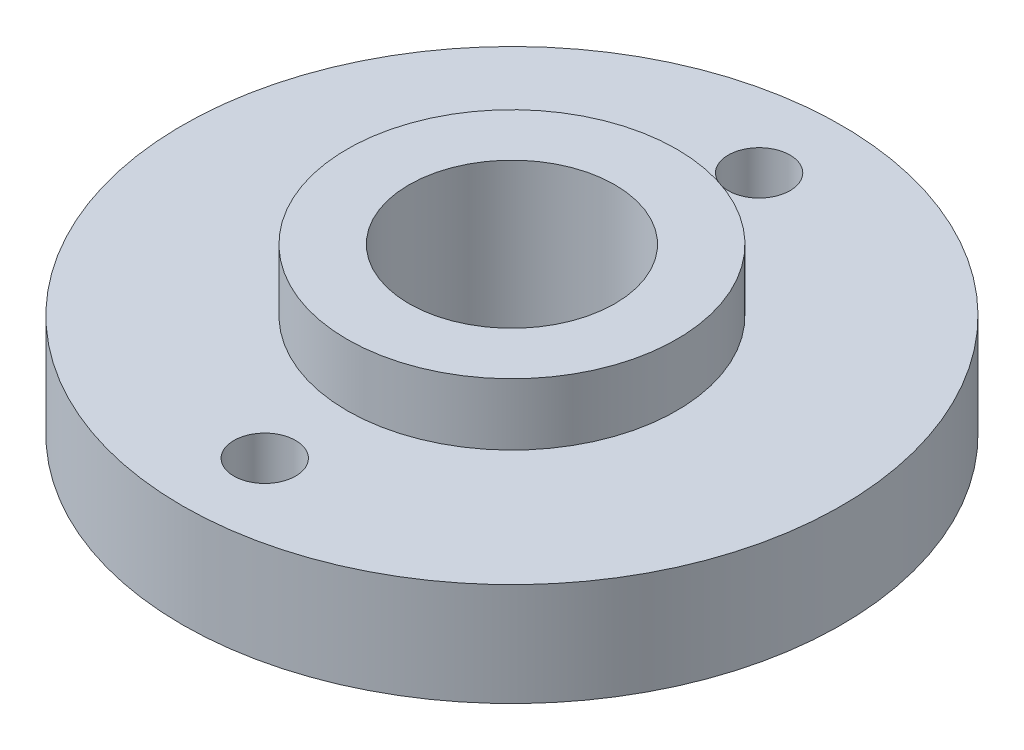
SolidWorks part; units mm, degrees
ref_plane "Спереди" through (0, 0, 0) normal (0, 0, 1) x (1, 0, 0)
ref_plane "Сверху" through (0, 0, 0) normal (0, 1, 0) x (1, 0, 0)
ref_plane "Справа" through (0, 0, 0) normal (1, 0, 0) x (0, 0, -1)
sketch "Эскиз2" plane through (0, 0, 0) normal (1, 0, 0) x (0, 0, -1)
  line L0 (0, 18.0956) -> (0, 0) construction
  line L1 (5, 0) -> (16, 0)
  line L2 (16, 0) -> (16, 5)
  line L3 (16, 5) -> (8, 5)
  line L4 (8, 5) -> (8, 8)
  line L5 (8, 8) -> (5, 8)
  line L6 (5, 8) -> (5, 0)
  dimension "D1" = 5
  dimension "D2" = 8
  dimension "D3" = 3
  dimension "D4" = 5
  dimension "D5" = 3
revolve "Повернуть1" add sketch "Эскиз2" angle 360 about L0
sketch "Эскиз3" plane through (0, 5, 0) normal (0, 1, 0) x (1, 0, 0)
  line L0 (0, 22.2403) -> (0, -28.6554) construction
  line L1 (-26.0144, 0) -> (30.2926, 0) construction
  circle A0 centre (0, 12) radius 1.5
  circle A1 centre (0, -12) radius 1.5
  circle A6 centre (0, 0) radius 12
  point P7 (0, 0)
  point P10 (0, 0)
  dimension "D1" = 3
  dimension "D2" = 3
  dimension "D3" = 12
extrude "Вырез-Вытянуть4" cut sketch "Эскиз3" against normal through all contours A0
extrude "Вырез-Вытянуть5" cut sketch "Эскиз3<4>" against normal through all contours A1
sketch "Эскиз3<4>" plane through (0, 5, 0) normal (0, 1, 0) x (1, 0, 0) same geometry as "Эскиз3"
